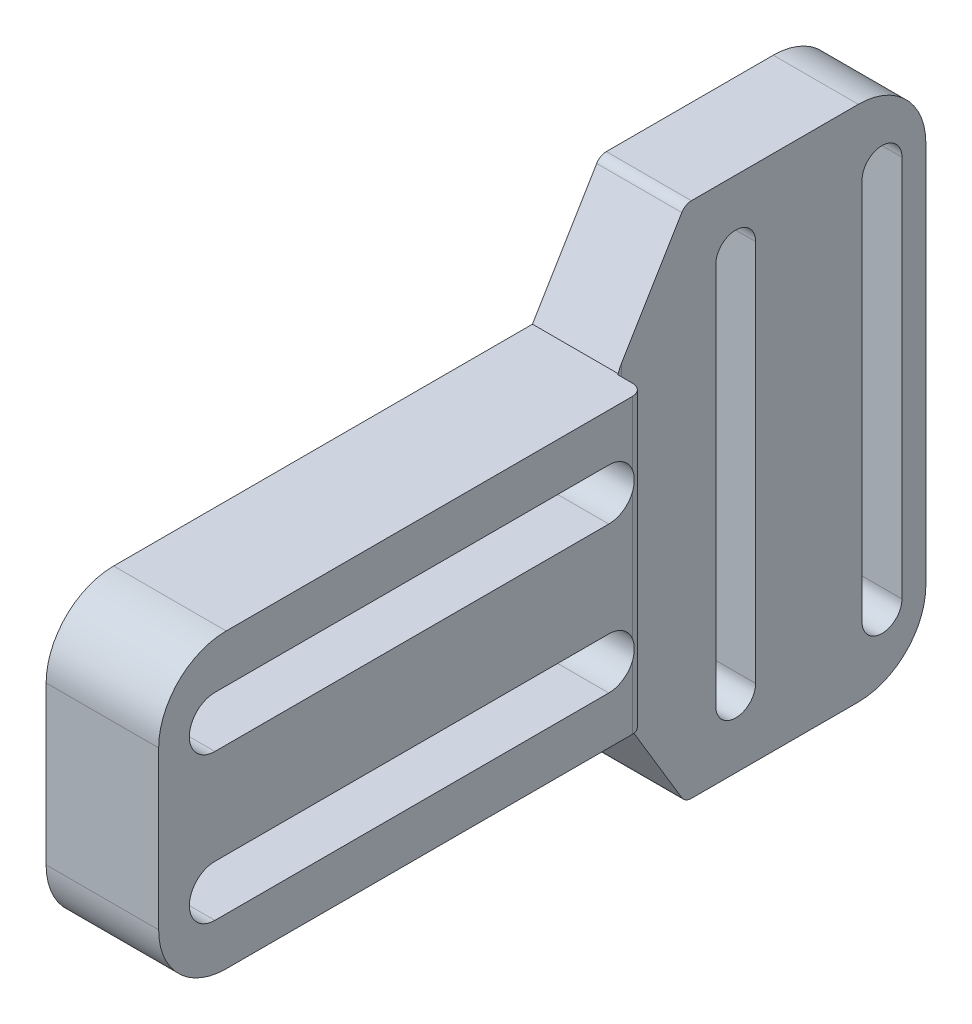
SolidWorks part; units mm, degrees
ref_plane "Front Plane" through (0, 0, 0) normal (0, 0, 1) x (1, 0, 0)
ref_plane "Top Plane" through (0, 0, 0) normal (0, 1, 0) x (1, 0, 0)
ref_plane "Right Plane" through (0, 0, 0) normal (1, 0, 0) x (0, 0, -1)
sketch "Sketch1" plane through (21.5125, 0, 0) normal (1, 0, 0) x (0, 0, -1)
  line L0 (-76.4447, 56.6417) -> (-31.9947, 56.6417) construction
  line L1 (-82.7947, 64.8967) -> (35.4637, 64.8967)
  line L2 (-82.7947, 64.8967) -> (-82.7947, 31.8767)
  line L3 (-82.7947, 31.8767) -> (35.4637, 31.8767)
  line L4 (35.4637, 64.8967) -> (35.4637, 31.8767)
  line L5 (-76.4447, 59.5267) -> (-31.9947, 59.5267)
  line L6 (-76.4447, 53.7567) -> (-31.9947, 53.7567)
  line L7 (-82.7947, 48.3867) -> (35.4637, 48.3867) construction
  line L8 (-23.6655, 48.3867) -> (-23.6655, 64.8967) construction
  line L9 (-76.4447, 40.1317) -> (-31.9947, 40.1317) construction
  line L10 (-76.4447, 37.2467) -> (-31.9947, 37.2467)
  line L11 (-76.4447, 43.0167) -> (-31.9947, 43.0167)
  arc A0 (-76.4447, 59.5267) -> (-76.4447, 53.7567) centre (-76.4447, 56.6417) ccw
  arc A1 (-31.9947, 53.7567) -> (-31.9947, 59.5267) centre (-31.9947, 56.6417) ccw
  arc A2 (-76.4447, 37.2467) -> (-76.4447, 43.0167) centre (-76.4447, 40.1317) cw
  arc A3 (-31.9947, 43.0167) -> (-31.9947, 37.2467) centre (-31.9947, 40.1317) cw
  point P6 (-54.2197, 56.6417)
  point P15 (-23.6655, 56.6417)
  point P18 (-54.2197, 40.1317)
  dimension "D1" = 2.885
  dimension "D2" = 44.45
  dimension "D3" = 6.35
  dimension "D4" = 8.255
extrude "Boss-Extrude1" add sketch "Sketch1" along normal blind 12.7
sketch "Sketch2" plane through (0, 64.8967, 0) normal (0, 1, 0) x (1, 0, 0)
  line L0 (34.2125, 35.4637) -> (21.5125, 35.4637) construction
  line L1 (31.1125, 35.4637) -> (34.2125, 35.4637)
  line L2 (31.1125, 35.4637) -> (31.1125, -28.0363)
  line L3 (31.1125, -28.0363) -> (34.2125, -28.0363)
  line L4 (34.2125, 35.4637) -> (34.2125, -28.0363)
  line L5 (34.2125, 35.4637) -> (34.2125, -82.7947) construction
  dimension "D1" = 3.1
  dimension "D2" = 63.5
extrude "Cut-Extrude1" cut sketch "Sketch2" against normal through all contours L2 L3 L4 L1
chamfer "Chamfer1" distance 0.127 angle 45 1 edges at (31.1125, 48.3867, 28.0363)
sketch "Sketch5" plane through (31.1125, 0, 0) normal (1, 0, 0) x (0, 0, -1)
  line L0 (-27.9093, 48.3867) -> (49.1425, 48.3867) construction
  line L1 (-27.9093, 64.8967) -> (-27.9093, 31.8767) construction
  line L2 (35.4637, 31.8767) -> (35.4637, 64.8967) construction
  line L3 (-27.9093, 48.3867) -> (35.4637, 48.3867)
  line L4 (-27.9093, 19.1767) -> (-27.9093, 77.5967)
  line L5 (-27.9093, 77.5967) -> (35.4637, 77.5967)
  line L6 (35.4637, 19.1767) -> (35.4637, 77.5967)
  line L7 (35.4637, 64.8967) -> (-27.9093, 64.8967) construction
  line L8 (-27.9093, 19.1767) -> (35.4637, 19.1767)
  line M6 (35.4637, 64.8967) -> (-27.9093, 64.8967)
  line M8 (-27.9093, 31.8767) -> (35.4637, 31.8767)
  dimension "D1" = 12.7
extrude "Boss-Extrude2" add sketch "Sketch5" along direction (1, 0, 0) on the side against the normal up to vertex (9.6 mm away) contours L4 L8 L6 M8 | L6 L5 L4 M6 region at (31.1125, 25.5267, -3.7772) region at (31.1125, 71.2467, -3.7772) up to point (21.5125, 64.8967, -35.4637)
sketch "Sketch3" plane through (31.1125, 0, 0) normal (1, 0, 0) x (0, 0, -1)
  line L0 (1.9357, 69.9767) -> (1.9357, 26.7967) construction
  line L1 (4.1857, 69.9767) -> (4.1857, 26.7967)
  line L2 (-0.3143, 69.9767) -> (-0.3143, 26.7967)
  line L3 (35.4637, 48.3867) -> (-82.7947, 48.3867) construction
  line L4 (35.4637, 19.1767) -> (35.4637, 77.5967) construction
  line L5 (-82.7947, 64.8967) -> (-82.7947, 31.8767) construction
  line L6 (35.4637, 64.8967) -> (-27.9093, 64.8967) construction
  line L7 (-6.3193, 31.8767) -> (-6.3193, 64.8967) construction
  line L8 (35.4637, 31.8767) -> (-27.9093, 31.8767) construction
  line L9 (-14.5743, 69.9767) -> (-14.5743, 26.7967) construction
  line L10 (-16.8243, 69.9767) -> (-16.8243, 26.7967)
  line L11 (-12.3243, 69.9767) -> (-12.3243, 26.7967)
  line L12 (-27.9093, 64.8967) -> (-27.9093, 31.8767) construction
  arc A0 (4.1857, 69.9767) -> (-0.3143, 69.9767) centre (1.9357, 69.9767) ccw
  arc A1 (-0.3143, 26.7967) -> (4.1857, 26.7967) centre (1.9357, 26.7967) ccw
  arc A2 (-16.8243, 69.9767) -> (-12.3243, 69.9767) centre (-14.5743, 69.9767) cw
  arc A3 (-12.3243, 26.7967) -> (-16.8243, 26.7967) centre (-14.5743, 26.7967) cw
  point P2 (1.9357, 48.3867)
  point P21 (-14.5743, 48.3867)
  dimension "D1" = 2.25
  dimension "D2" = 43.18
  dimension "D3" = 13.335
  dimension "D4" = 8.255
extrude "Cut-Extrude2" cut sketch "Sketch3" against normal through all
sketch "Sketch4" plane through (0, 77.5967, 0) normal (0, 1, 0) x (1, 0, 0)
  line L0 (31.6725, 32.911) -> (31.6725, 17.671) construction
  line L1 (21.5125, 35.4637) -> (31.6725, 35.4637)
  line L2 (21.5125, 35.4637) -> (21.5125, 6.8887)
  line L3 (21.5125, 6.8887) -> (31.6725, 6.8887)
  line L4 (31.6725, 35.4637) -> (31.6725, 6.8887)
  dimension "D1" = 28.575
extrude "Cut-Extrude3" cut sketch "Sketch4" against normal through all
sketch "Sketch6" plane through (31.1125, 0, 0) normal (1, 0, 0) x (0, 0, -1)
  line L0 (-27.9093, 64.8967) -> (-20.2893, 77.5967)
  line L1 (-27.9093, 64.8967) -> (-27.9093, 77.5967) construction
  line L2 (-27.9093, 77.5967) -> (6.8887, 77.5967) construction
  line L3 (-20.2893, 77.5967) -> (-27.9093, 77.5967)
  line L4 (-27.9093, 77.5967) -> (-27.9093, 64.8967)
  line L5 (-27.9093, 48.3867) -> (-8.612, 48.3867) construction
  line L6 (-27.9093, 64.8967) -> (-27.9093, 31.8767) construction
  line L7 (-20.2893, 19.1767) -> (-27.9093, 19.1767)
  line L8 (-27.9093, 31.8767) -> (-20.2893, 19.1767)
  line L9 (-27.9093, 19.1767) -> (-27.9093, 31.8767)
  dimension "D2" = 7.62
extrude "Cut-Extrude4" cut sketch "Sketch6" against normal through all
fillet "Fillet1" radius 7.62 4 edges at (26.3125, 19.1767, -6.8887) (26.3125, 77.5967, -6.8887) (27.8625, 31.8767, 82.7947) (27.8625, 64.8967, 82.7947)
fillet "Fillet2" radius 1.27 4 edges at (31.1125, 48.3867, 27.9093) (34.2125, 48.3867, 28.0363) (26.3125, 77.5967, 20.2893) (26.3125, 19.1767, 20.2893)
